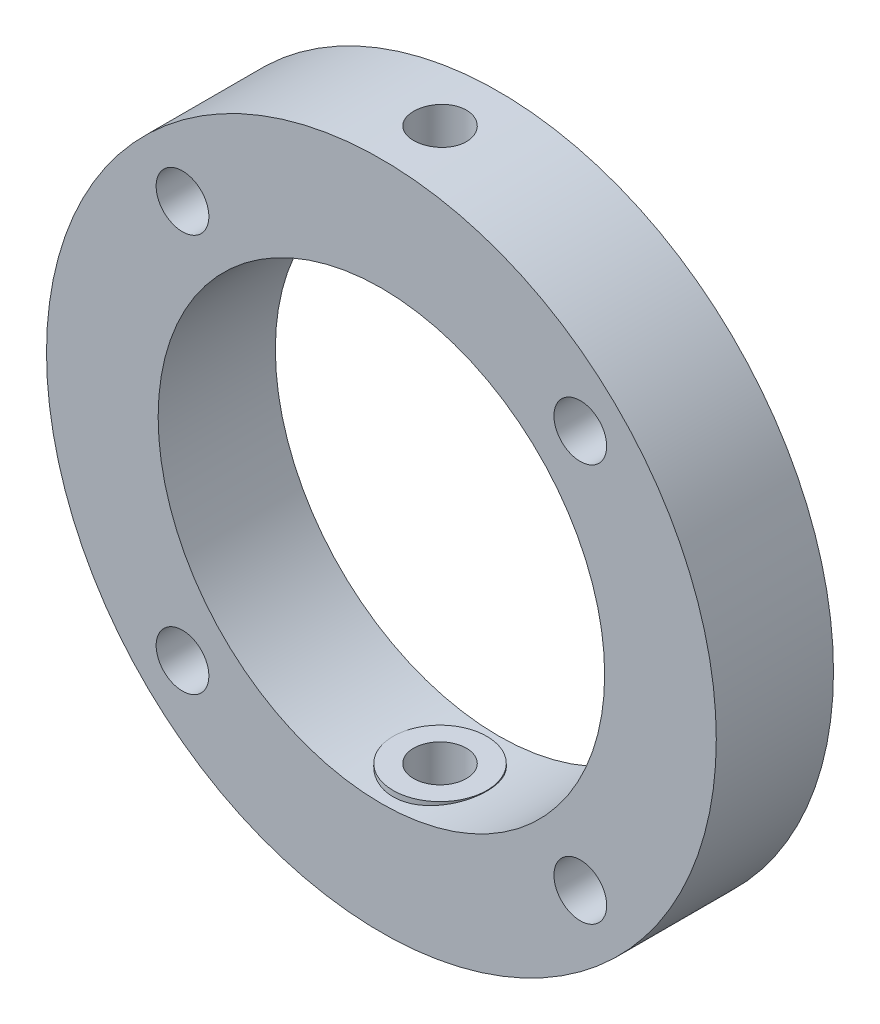
SolidWorks part; units mm, degrees
ref_plane "Front Plane" through (0, 0, 0) normal (0, 0, 1) x (1, 0, 0)
ref_plane "Top Plane" through (0, 0, 0) normal (0, 1, 0) x (1, 0, 0)
ref_plane "Right Plane" through (0, 0, 0) normal (1, 0, 0) x (0, 0, -1)
sketch "Sketch1" plane through (0, 0, 0) normal (0, 0, 1) x (1, 0, 0)
  circle A0 centre (0, 0) radius 28.575
  dimension "D1" = 57.15
extrude "Boss-Extrude1" add sketch "Sketch1" along normal blind 10
sketch "Sketch2" plane through (0, 0, 10) normal (0, 0, 1) x (1, 0, 0)
  circle A0 centre (0, 0) radius 19.05
  dimension "D1" = 38.1
extrude "Cut-Extrude1" cut sketch "Sketch2" against normal through all
ref_plane "Plane1" through (0, 28.575, 0) normal (0, 1, 0) x (1, 0, 0)
sketch "Sketch5" plane through (0, 28.575, 0) normal (0, 1, 0) x (1, 0, 0)
  circle A0 centre (0, -5) radius 2.25
  dimension "D2" = 4.5
  dimension "D1" = 5
extrude "Cut-Extrude2" cut sketch "Sketch5" against normal through all
sketch "Sketch6" plane through (0, 0, 10) normal (0, 0, 1) x (1, 0, 0)
  line L0 (0, 28.575) -> (0, -28.575) construction
  line L1 (5.5, 28.575) -> (-5.5, 28.575) construction
  line L2 (0, 0) -> (-16.9706, 16.9706) construction
  circle A1 centre (0, 0) radius 28.575 construction
  circle A3 centre (0, 0) radius 24 construction
  circle A4 centre (-16.9706, 16.9706) radius 2.25
  circle A5 centre (16.9706, 16.9706) radius 2.25
  circle A6 centre (16.9706, -16.9706) radius 2.25
  circle A7 centre (-16.9706, -16.9706) radius 2.25
  point P21 (0, 0)
  dimension "D2" = 45
  dimension "D1" = 48
  dimension "D3" = 4.5
  dimension "D4" = 4
extrude "Cut-Extrude3" cut sketch "Sketch6" against normal through all
ref_plane "Offset to Inner Ring" through (0, 18.575, 0) normal (0, 1, 0) x (1, 0, 0)
sketch "Sketch7" plane through (0, 28.575, 0) normal (0, 1, 0) x (1, 0, 0)
  circle A0 centre (0, -5) radius 4
  circle A3 centre (0, -5) radius 2.25
  circle A5 centre (0, -5) radius 2.25 construction
  dimension "D1" = 8
extrude "Boss-Extrude2" add sketch "Sketch7" along normal blind 3 from surface starting at plane "Offset to Inner Ring"
ref_plane "Other Side Plane" through (0, -18.575, 0) normal (0, 1, 0) x (1, 0, 0)
extrude "Boss-Extrude3" add sketch "Sketch7<3>" against normal up to surface (0.475 mm away) from surface up to face at (19.05, 0, 10) starting at plane "Other Side Plane"
sketch "Sketch7<3>" plane through (0, 28.575, 0) normal (0, 1, 0) x (1, 0, 0) same geometry as "Sketch7"
